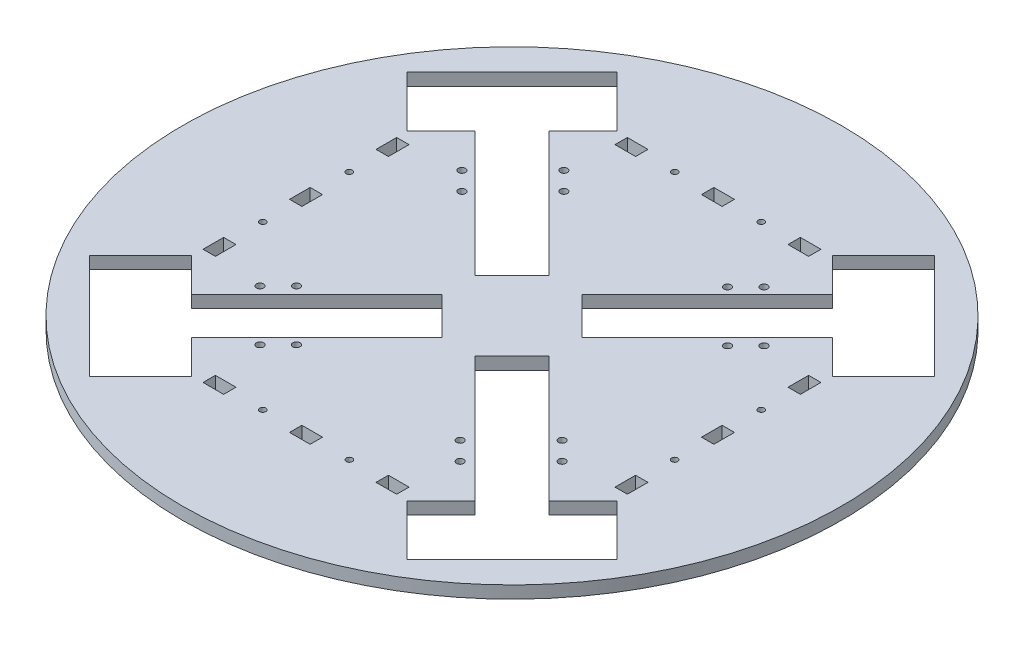
SolidWorks part; units mm, degrees
ref_plane "Front Plane" through (0, 0, 0) normal (0, 0, 1) x (1, 0, 0)
ref_plane "Top Plane" through (0, 0, 0) normal (0, 1, 0) x (1, 0, 0)
ref_plane "Right Plane" through (0, 0, 0) normal (1, 0, 0) x (0, 0, -1)
sketch "Sketch1" plane through (0, 0, 0) normal (0, 1, 0) x (1, 0, 0)
  line L1 (0, 0) -> (-200, 0) construction
  line L2 (0, 0) -> (0, 200) construction
  line L3 (0, 200) -> (-200, 200) construction
  line L4 (-200, 0) -> (-200, 200) construction
  circle A0 centre (-100, 100) radius 160
  point P8 (-100, 200)
  point P9 (-200, 100)
  dimension "D3" = 320
  dimension "D1" = 200
  dimension "D2" = 200
extrude "Boss-Extrude1" add sketch "Sketch1" along normal blind 6 contours A0 region at (-100, 0, -100)
sketch "Sketch2" plane through (0, 6, 0) normal (0, 1, 0) x (1, 0, 0)
  line L0 (-260, 100) -> (60, 100) construction
  line L1 (-213.1371, -13.1371) -> (-100, 100) construction
  line L2 (-100, 100) -> (13.1371, 213.1371) construction
  line L3 (-213.1371, 213.1371) -> (13.1371, -13.1371) construction
  circle A0 centre (-100, 100) radius 160 construction
  dimension "D1" = 45
  dimension "D2" = 45
sketch "Sketch3" plane through (0, 0, 0) normal (0, -1, 0) x (1, 0, 0)
  line L0 (-22.9254, -227.9863) -> (-47.6741, -203.2376)
  line L1 (-22.9254, -227.9863) -> (27.9863, -177.0746)
  line L2 (-47.6741, -203.2376) -> (3.2376, -152.3259)
  line L3 (27.9863, -177.0746) -> (3.2376, -152.3259)
  line L4 (3.2376, -47.6741) -> (27.9863, -22.9254)
  line L5 (3.2376, -47.6741) -> (-47.6741, 3.2376)
  line L6 (27.9863, -22.9254) -> (-22.9254, 27.9863)
  line L7 (-47.6741, 3.2376) -> (-22.9254, 27.9863)
  line L8 (-152.3259, 3.2376) -> (-177.0746, 27.9863)
  line L9 (-152.3259, 3.2376) -> (-203.2376, -47.6741)
  line L10 (-177.0746, 27.9863) -> (-227.9863, -22.9254)
  line L11 (-203.2376, -47.6741) -> (-227.9863, -22.9254)
  line L12 (-177.0746, -227.9863) -> (-152.3259, -203.2376)
  line L13 (-177.0746, -227.9863) -> (-227.9863, -177.0746)
  line L14 (-152.3259, -203.2376) -> (-203.2376, -152.3259)
  line L15 (-227.9863, -177.0746) -> (-203.2376, -152.3259)
  line L16 (-213.1371, -213.1371) -> (13.1371, 13.1371) construction
  line L17 (-100, -100) -> (13.1371, -213.1371) construction
  line L18 (-213.1371, 13.1371) -> (-100, -100) construction
  point P26 (2.5305, -202.5305)
  point P27 (2.5305, 2.5305)
  point P28 (-202.5305, 2.5305)
  point P29 (-202.5305, -202.5305)
  dimension "D1" = 35
  dimension "D2" = 15
  dimension "D3" = 15
  dimension "D4" = 15
  dimension "D5" = 15
  dimension "D6" = 72
extrude "Cut-Extrude1" cut sketch "Sketch3" against normal through all
sketch "Sketch4" plane through (0, 0, 0) normal (0, -1, 0) x (1, 0, 0)
  line L0 (-13.2026, -31.2339) -> (-31.2339, -13.2026)
  line L1 (-13.2026, -31.2339) -> (-74.0138, -92.045)
  line L2 (-31.2339, -13.2026) -> (-92.045, -74.0138)
  line L3 (-74.0138, -92.045) -> (-92.045, -74.0138)
  line L4 (-168.7661, -13.2026) -> (-186.7974, -31.2339)
  line L5 (-168.7661, -13.2026) -> (-107.955, -74.0138)
  line L6 (-186.7974, -31.2339) -> (-125.9862, -92.045)
  line L7 (-107.955, -74.0138) -> (-125.9862, -92.045)
  line L8 (-203.2376, -47.6741) -> (-152.3259, 3.2376) construction
  line L9 (-186.7974, -168.7661) -> (-125.9862, -107.955)
  line L10 (-186.7974, -168.7661) -> (-168.7661, -186.7974)
  line L11 (-125.9862, -107.955) -> (-107.955, -125.9862)
  line L12 (-168.7661, -186.7974) -> (-107.955, -125.9862)
  line L13 (-13.2026, -168.7661) -> (-31.2339, -186.7974)
  line L14 (-13.2026, -168.7661) -> (-74.0138, -107.955)
  line L15 (-31.2339, -186.7974) -> (-92.045, -125.9862)
  line L16 (-74.0138, -107.955) -> (-92.045, -125.9862)
  line L17 (-100, -100) -> (13.1371, -213.1371) construction
  line L18 (-213.1371, -213.1371) -> (13.1371, 13.1371) construction
  line L19 (-213.1371, 13.1371) -> (-100, -100) construction
  line L20 (-47.6741, 3.2376) -> (3.2376, -47.6741) construction
  line L21 (-152.3259, -203.2376) -> (-203.2376, -152.3259) construction
  line L22 (3.2376, -152.3259) -> (-47.6741, -203.2376) construction
  point P22 (-83.0294, -116.9706)
  point P23 (-116.9706, -83.0294)
  point P26 (-83.0294, -83.0294)
  point P27 (-116.9706, -116.9706)
  point P35 (-100, -100)
  point P36 (-100, -100)
  line M20 (-203.2376, -152.3259) -> (-152.3259, -203.2376)
  line M22 (-152.3259, 3.2376) -> (-203.2376, -47.6741)
  line M26 (3.2376, -47.6741) -> (-47.6741, 3.2376)
  line M32 (-47.6741, -203.2376) -> (3.2376, -152.3259)
  dimension "D1" = 25.5
  dimension "D2" = 86
extrude "Cut-Extrude2" cut sketch "Sketch4" against normal through all contours L14 L16 L15 M32 | L12 L11 L9 M20 | L7 L5 L6 M22 | L3 L1 L2 M26 region at (-52.6238, 0, -52.6238) region at (-147.3762, 0, -52.6238) region at (-147.3762, 0, -147.3762) region at (-52.6238, 0, -147.3762)
sketch "Sketch7" plane through (0, 0, 0) normal (0, -1, 0) x (1, 0, 0)
  line L0 (-152.3259, -203.2376) -> (-168.7661, -186.7974) construction
  line L1 (-168.7661, -186.7974) -> (-107.955, -125.9862) construction
  line L2 (-152.3259, -203.2376) -> (-168.7661, -186.7974) construction
  line L3 (-168.7661, -186.7974) -> (-107.955, -125.9862) construction
  circle A2 centre (-149.0025, -26.673) radius 1.75
  circle A10 centre (-148.5782, -173.7512) radius 1.75
  circle A20 centre (-140.1637, -35.5119) radius 1.75
  circle A21 centre (-164.9124, -60.2606) radius 1.75
  circle A22 centre (-173.7512, -51.4218) radius 1.75
  circle A25 centre (-173.327, -149.0025) radius 1.75
  circle A26 centre (-164.4881, -140.1637) radius 1.75
  circle A27 centre (-139.7394, -164.9124) radius 1.75
  circle A32 centre (-26.673, -50.9975) radius 1.75
  circle A33 centre (-35.5119, -59.8363) radius 1.75
  circle A34 centre (-60.2606, -35.0876) radius 1.75
  circle A35 centre (-51.4218, -26.2488) radius 1.75
  circle A36 centre (-50.9975, -173.327) radius 1.75
  circle A37 centre (-59.8363, -164.4881) radius 1.75
  circle A38 centre (-35.0876, -139.7394) radius 1.75
  circle A39 centre (-26.2488, -148.5782) radius 1.75
  point P29 (-100, -100)
  dimension "D9" = 3.5
  dimension "D1" = 12.5
  dimension "D2" = 35
  dimension "D3" = 35
  dimension "D4" = 12.5
  dimension "D5" = 37.1652
  dimension "D6" = 23.5
  dimension "D7" = 5.05
  dimension "D8" = 29.95
  dimension "D10" = 4
extrude "Cut-Extrude3" cut sketch "Sketch7" against normal through all
sketch "Sketch8" plane through (0, 6, 0) normal (0, 1, 0) x (1, 0, 0)
  line L1 (0, 200) -> (-200, 200) construction
  line L2 (0, 200) -> (0, 0) construction
  line L3 (0, 0) -> (-200, 0) construction
  line L4 (-200, 200) -> (-200, 0) construction
  line L5 (0, 200) -> (-200, 0) construction
  line L6 (0, 0) -> (-200, 200) construction
  point P0 (-100, 100)
  dimension "D1" = 200
  dimension "D2" = 200
sketch "Sketch9" plane through (0, 0, 0) normal (0, -1, 0) x (1, 0, 0)
  line L0 (-3, -119.5) -> (-3, -122.5) construction
  line L1 (-3, -122.5) -> (3, -122.5) construction
  line L2 (3, -122.5) -> (3, -119.5) construction
  line L3 (3, -119.5) -> (-3, -119.5) construction
  line L4 (-3, -77.5) -> (-3, -80.5) construction
  line L5 (-3, -80.5) -> (3, -80.5) construction
  line L6 (3, -80.5) -> (3, -77.5) construction
  line L7 (3, -77.5) -> (-3, -77.5) construction
  line L8 (3, -147) -> (3, -137) construction
  line L9 (3, -137) -> (-3, -137) construction
  line L10 (-3, -137) -> (-3, -147) construction
  line L11 (-3, -147) -> (3, -147) construction
  line L12 (3, -105) -> (3, -95) construction
  line L13 (3, -95) -> (-3, -95) construction
  line L14 (-3, -95) -> (-3, -105) construction
  line L15 (-3, -105) -> (3, -105) construction
  line L16 (3, -63) -> (3, -53) construction
  line L17 (3, -53) -> (-3, -53) construction
  line L18 (-3, -53) -> (-3, -63) construction
  line L19 (-3, -63) -> (3, -63) construction
  line L20 (-3, -119.5) -> (-3, -122.5) construction
  line L21 (-3, -122.5) -> (3, -122.5) construction
  line L22 (3, -122.5) -> (3, -119.5) construction
  line L23 (3, -119.5) -> (-3, -119.5) construction
  line L24 (-3, -77.5) -> (-3, -80.5) construction
  line L25 (-3, -80.5) -> (3, -80.5) construction
  line L26 (3, -80.5) -> (3, -77.5) construction
  line L27 (3, -77.5) -> (-3, -77.5) construction
  line L28 (3, -147) -> (3, -137)
  line L29 (3, -137) -> (-3, -137)
  line L30 (-3, -137) -> (-3, -147)
  line L31 (-3, -147) -> (3, -147)
  line L32 (3, -105) -> (3, -95)
  line L33 (3, -95) -> (-3, -95)
  line L34 (-3, -95) -> (-3, -105)
  line L35 (-3, -105) -> (3, -105)
  line L36 (3, -63) -> (3, -53)
  line L37 (3, -53) -> (-3, -53)
  line L38 (-3, -53) -> (-3, -63)
  line L39 (-3, -63) -> (3, -63)
  circle A0 centre (0, -79) radius 1.5
  circle A1 centre (0, -121) radius 1.5
  point P10 (0, 0)
  point P12 (3, -79)
  point P15 (0, -80.5)
  point P22 (3, -121)
extrude "Cut-Extrude4" cut sketch "Sketch9" against normal through all
pattern_circular "CirPattern1" count 4 over 360 about axis through (-100, 0, -100) along (0, 1, 0) of "Cut-Extrude4"
